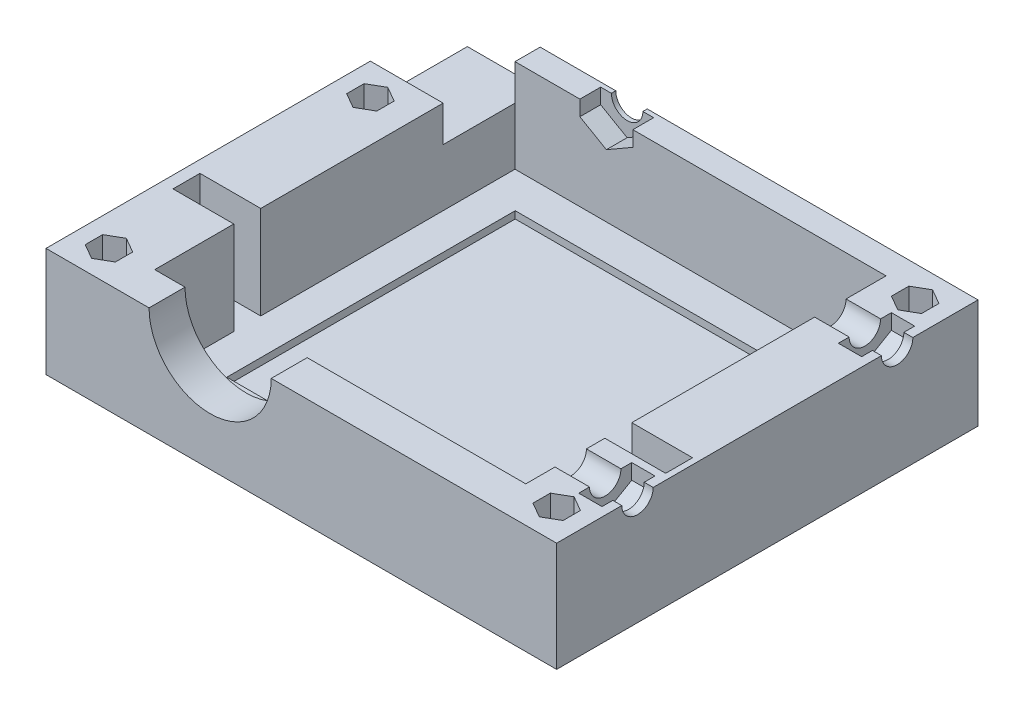
SolidWorks part; units mm, degrees
material "PLA"
ref_plane "Front Plane" through (0, 0, 0) normal (0, 0, 1) x (1, 0, 0)
ref_plane "Top Plane" through (0, 0, 0) normal (0, 1, 0) x (1, 0, 0)
ref_plane "Right Plane" through (0, 0, 0) normal (1, 0, 0) x (0, 0, -1)
sketch "Sketch1" plane through (0, 0, 0) normal (0, 1, 0) x (1, 0, 0)
  line L1 (28.4162, -23.45) -> (-28.4163, -23.45)
  line L2 (28.4162, -23.45) -> (28.4162, 23.45)
  line L3 (28.4162, 23.45) -> (-28.4163, 23.45)
  line L4 (-28.4163, -23.45) -> (-28.4163, 23.45)
  line L5 (28.4162, -23.45) -> (-28.4163, 23.45) construction
  line L6 (28.4162, 23.45) -> (-28.4163, -23.45) construction
  point P0 (0, 0)
  dimension "D1" = 56.8325
  dimension "D2" = 46.9
extrude "Boss-Extrude1" add sketch "Sketch1" along normal blind 12.17
sketch "Sketch2" plane through (0, 12.17, 0) normal (0, 1, 0) x (1, 0, 0)
  line L0 (-28.4163, -23.45) -> (-20.3162, -23.45) construction
  line L1 (-28.4163, -23.45) -> (28.4162, -23.45) construction
  line L2 (-20.3162, -23.45) -> (-20.3162, -19.45) construction
  line L4 (-20.3162, -19.45) -> (20.9838, -19.45)
  line L5 (-20.3162, -19.45) -> (-20.3162, 20.65)
  line L6 (-20.3162, 20.65) -> (20.9838, 20.65)
  line L7 (20.9838, -19.45) -> (20.9838, 20.65)
  dimension "D1" = 8.1
  dimension "D2" = 4
  dimension "D3" = 41.3
  dimension "D4" = 40.1
extrude "Cut-Extrude1" cut sketch "Sketch2" against normal blind 10.37
sketch "Sketch3" plane through (0, 1.8, 0) normal (0, 1, 0) x (1, 0, 0)
  line L0 (20.9838, 20.65) -> (20.9838, 16.6622) construction
  line L1 (20.9838, -19.45) -> (20.9838, 20.65) construction
  line L2 (20.9838, 16.6622) -> (16.996, 16.6622) construction
  line L4 (16.996, 16.6622) -> (-16.3041, 16.6622)
  line L5 (16.996, 16.6622) -> (16.996, -15.4378)
  line L6 (16.996, -15.4378) -> (-16.3041, -15.4378)
  line L7 (-16.3041, 16.6622) -> (-16.3041, -15.4378)
  dimension "D1" = 3.9878
  dimension "D2" = 3.9878
  dimension "D3" = 32.1
  dimension "D4" = 33.3
extrude "Cut-Extrude2" cut sketch "Sketch3" against normal blind 0.8
sketch "Sketch4" plane through (0, 12.17, 0) normal (0, 1, 0) x (1, 0, 0)
  line L0 (-20.3162, 20.65) -> (-20.3162, -19.45) construction
  line L1 (-28.4163, 23.45) -> (-20.3162, 23.45)
  line L2 (-28.4163, 23.45) -> (-28.4163, 12.65)
  line L3 (-28.4163, 12.65) -> (-20.3162, 12.65)
  line L4 (-20.3162, 23.45) -> (-20.3162, 12.65)
  dimension "D1" = 10.8
extrude "Cut-Extrude3" cut sketch "Sketch4" against normal blind 4
sketch "Sketch5" plane through (0, 12.17, 0) normal (0, 1, 0) x (1, 0, 0)
  line L0 (-28.4163, 12.65) -> (-28.4163, -7.65)
  line L1 (-28.4163, 12.65) -> (-28.4163, -23.45) construction
  line L2 (-28.4163, -7.65) -> (-27.0813, -7.65)
  line L3 (-20.3162, 20.65) -> (-20.3162, -19.45) construction
  line L4 (-27.0813, -7.65) -> (-20.3162, -7.65)
  line L5 (-27.0813, -7.65) -> (-27.0813, -10.65)
  line L6 (-27.0813, -10.65) -> (-20.3162, -10.65)
  line L7 (-20.3162, -7.65) -> (-20.3162, -10.65)
  line M11 (-20.3162, -19.45) -> (-20.3162, 12.65)
  dimension "D1" = 20.3
  dimension "D2" = 1.335
  dimension "D3" = 3
extrude "Cut-Extrude4" cut sketch "Sketch5" against normal up to surface (10.37 mm away) contours L5 L6 L4 M11 | L5 L4 L7 L6 region at (-23.6987, 12.17, 9.15) up to face at (0.3338, 1.8, -0.6)
sketch "Sketch6" plane through (0, 12.17, 0) normal (0, 1, 0) x (1, 0, 0)
  line L0 (-20.3162, -10.65) -> (20.9838, -10.65) construction
  line L2 (20.9838, -19.45) -> (20.9838, 20.65) construction
  line L3 (20.9838, -10.65) -> (27.7488, -10.65)
  line L4 (20.9838, -10.65) -> (20.9838, -7.65)
  line L5 (20.9838, -7.65) -> (27.7488, -7.65)
  line L6 (27.7488, -10.65) -> (27.7488, -7.65)
  line M15 (20.9838, 20.65) -> (20.9838, -19.45)
  dimension "D1" = 6.765
extrude "Cut-Extrude5" cut sketch "Sketch6" against normal up to surface (10.37 mm away) contours L3 L6 L5 M15 region at (24.3663, 12.17, 9.15) up to face at (-11.6825, 1.8, 4.275)
sketch "Sketch7" plane through (0, 0, 23.45) normal (0, 0, 1) x (1, 0, 0)
  line L0 (-28.4163, 12.17) -> (-16.9462, 12.17) construction
  line L1 (-28.4163, 12.17) -> (28.4162, 12.17) construction
  line L2 (-16.9462, 12.17) -> (-3.3462, 12.17)
  line L3 (-16.9462, 12.17) -> (-16.9462, 5.37) construction
  line L4 (-16.9462, 5.37) -> (-10.1462, 5.37) construction
  arc A0 (-16.9462, 12.17) -> (-3.3462, 12.17) centre (-10.1462, 12.17) ccw
  line M8 (28.4162, 12.17) -> (-28.4163, 12.17)
  dimension "D1" = 13.6
  dimension "D2" = 6.8
  dimension "D3" = 6.8
  dimension "D4" = 11.47
extrude "Cut-Extrude6" cut sketch "Sketch7" against normal up to surface (4 mm away) contours A0 M8 region at (-10.1462, 9.284, 23.45) up to face at (0.3338, 6.985, 19.45)
sketch "Sketch8" plane through (0, 12.17, 0) normal (0, 1, 0) x (1, 0, 0)
  line L0 (-28.4163, -23.45) -> (-24.9163, -23.45) construction
  line L1 (-28.4163, -23.45) -> (-16.9462, -23.45) construction
  line L2 (-24.9163, -23.45) -> (-24.9163, -21.8752) construction
  line L3 (-24.9163, -21.8752) -> (-24.9163, -18.007) construction
  line L4 (-24.9163, -18.007) -> (-24.9163, 7.2248) construction
  line L5 (-24.9163, -18.007) -> (-26.5913, -18.974)
  line L6 (-26.5913, -18.974) -> (-26.5913, -20.9081)
  line L7 (-26.5913, -20.9081) -> (-24.9163, -21.8752)
  line L8 (-24.9163, -21.8752) -> (-23.2413, -20.9081)
  line L9 (-23.2413, -20.9081) -> (-23.2413, -18.974)
  line L10 (-23.2413, -18.974) -> (-24.9163, -18.007)
  line L11 (-24.9163, 7.2248) -> (-24.9163, 11.093) construction
  line L12 (-24.9163, -21.8752) -> (24.9162, -21.8752) construction
  line L13 (-24.9163, 11.093) -> (-26.5913, 10.126)
  line L14 (-26.5913, 10.126) -> (-26.5913, 8.1918)
  line L15 (-26.5913, 8.1918) -> (-24.9163, 7.2248)
  line L16 (-24.9163, 7.2248) -> (-23.2413, 8.1918)
  line L17 (-23.2413, 8.1918) -> (-23.2413, 10.126)
  line L18 (-23.2413, 10.126) -> (-24.9163, 11.093)
  line L19 (24.9162, -21.8752) -> (24.9162, -18.007) construction
  line L20 (24.9162, -18.007) -> (24.9162, 18.0248) construction
  line L21 (24.9162, 18.0248) -> (24.9162, 21.893) construction
  line L23 (24.9162, 21.893) -> (23.2412, 20.926)
  line L24 (23.2412, 20.926) -> (23.2412, 18.9919)
  line L25 (23.2412, 18.9919) -> (24.9162, 18.0248)
  line L26 (24.9162, 18.0248) -> (26.5912, 18.9919)
  line L27 (26.5912, 18.9919) -> (26.5912, 20.926)
  line L28 (26.5912, 20.926) -> (24.9162, 21.893)
  line L29 (24.9162, -18.007) -> (23.2412, -18.974)
  line L30 (23.2412, -18.974) -> (23.2412, -20.9081)
  line L31 (23.2412, -20.9081) -> (24.9162, -21.8752)
  line L32 (24.9162, -21.8752) -> (26.5912, -20.9081)
  line L33 (26.5912, -20.9081) -> (26.5912, -18.974)
  line L34 (26.5912, -18.974) -> (24.9162, -18.007)
  circle A0 centre (-24.9163, -19.9411) radius 1.675 construction
  circle A1 centre (-24.9163, 9.1589) radius 1.675 construction
  circle A2 centre (24.9162, 19.9589) radius 1.675 construction
  circle A3 centre (24.9162, -19.9411) radius 1.675 construction
  dimension "D1" = 3.5
  dimension "D2" = 1.5748
  dimension "D3" = 3.8682
  dimension "D4" = 25.2318
  dimension "D5" = 3.8682
  dimension "D6" = 49.8325
  dimension "D7" = 3.8682
  dimension "D8" = 36.0318
  dimension "D9" = 3.8682
extrude "Cut-Extrude7" cut sketch "Sketch8" against normal blind 5.25
sketch "Sketch9" plane through (0, 6.92, 0) normal (0, 1, 0) x (1, 0, 0)
  line L0 (-24.9163, 11.093) -> (-24.9163, 7.2248) construction
  line L1 (-24.9163, 7.2248) -> (-24.2368, 7.2248) construction
  line L2 (-26.5913, 10.126) -> (-26.5913, 8.1918) construction
  line L3 (-26.5913, 9.1589) -> (-23.2413, 9.1589) construction
  line L4 (-23.2413, 8.1918) -> (-23.2413, 10.126) construction
  line L5 (-24.2368, 7.2248) -> (-24.2368, 8.0608) construction
  line L6 (-24.2368, 8.0608) -> (-25.5134, 8.0608) construction
  line L7 (-25.5134, 8.0608) -> (-25.5134, 10.257) construction
  line L8 (-24.9163, 9.1589) -> (-24.9163, -18.007) construction
  line L9 (-24.9163, -18.007) -> (-24.9163, -21.8752) construction
  line L10 (-24.9163, -21.8752) -> (24.9162, -21.8752) construction
  line L11 (24.9162, -21.8752) -> (24.9162, -18.007) construction
  line L12 (24.9162, -18.007) -> (24.9162, 18.0248) construction
  line L13 (24.9162, 18.0248) -> (24.9162, 21.893) construction
  circle A1 centre (-24.8751, 9.1589) radius 1.2702
  circle A2 centre (-24.9163, -19.9411) radius 1.2702
  circle A3 centre (24.9162, -19.9411) radius 1.2702
  circle A4 centre (24.9162, 19.9589) radius 1.2702
  dimension "D5" = 2.5404
  dimension "D6" = 2.5404
  dimension "D7" = 2.5404
  dimension "D8" = 2.5404
  dimension "D1" = 0.6794
  dimension "D2" = 0.836
  dimension "D3" = 1.2766
  dimension "D4" = 2.1963
extrude "Cut-Extrude8" cut sketch "Sketch9" against normal through all
sketch "Sketch10" plane through (0, 0, 23.45) normal (0, 0, 1) x (1, 0, 0)
  line L0 (-16.9462, 12.17) -> (-13.0962, 12.17) construction
  line L1 (-13.0962, 12.17) -> (-10.1462, 12.17) construction
  line L2 (-10.1462, 12.17) -> (-10.1462, 8.7636) construction
  line L4 (-10.1462, 8.7664) -> (-7.1986, 10.4682)
  line L5 (-7.1986, 10.4682) -> (-7.1986, 13.8718)
  line L6 (-7.1986, 13.8718) -> (-10.1462, 15.5736)
  line L7 (-10.1462, 15.5736) -> (-13.0938, 13.8718)
  line L8 (-13.0938, 13.8718) -> (-13.0938, 10.4682)
  line L9 (-13.0938, 10.4682) -> (-10.1462, 8.7664)
  arc A0 (-16.9462, 12.17) -> (-3.3462, 12.17) centre (-10.1462, 12.17) ccw construction
  circle A1 centre (-10.1462, 12.17) radius 2.9476 construction
  point P7 (-10.1462, 10.4668)
  dimension "D1" = 3.85
  dimension "D2" = 3.4064
  dimension "D3" = 2.95
  dimension "D4" = 3.4036
sketch "Sketch11" plane through (0, 0, -20.65) normal (0, 0, 1) x (1, 0, 0)
  line L0 (-13.0938, 10.4682) -> (-10.1462, 8.7664) construction
  line L1 (-10.1462, 8.7664) -> (-7.1986, 10.4682) construction
  line L2 (-7.1986, 10.4682) -> (-7.1986, 13.8718) construction
  line L3 (-13.0938, 13.8718) -> (-13.0938, 10.4682) construction
  line L4 (-10.1462, 15.5736) -> (-13.0938, 13.8718) construction
  line L5 (-7.1986, 13.8718) -> (-10.1462, 15.5736) construction
  line L6 (-13.0938, 10.4682) -> (-10.1462, 8.7664)
  line L7 (-10.1462, 8.7664) -> (-7.1986, 10.4682)
  line L8 (-7.1986, 10.4682) -> (-7.1986, 13.8718)
  line L9 (-13.0938, 13.8718) -> (-13.0938, 10.4682)
  line L10 (-10.1462, 15.5736) -> (-13.0938, 13.8718)
  line L11 (-7.1986, 13.8718) -> (-10.1462, 15.5736)
extrude "Cut-Extrude10" cut sketch "Sketch11" against normal blind 2.3114
sketch "Sketch12" plane through (0, 0, -22.9614) normal (0, 0, 1) x (1, 0, 0)
  line L5 (-13.0938, 12.17) -> (-13.0938, 10.4682)
  line L6 (-13.0938, 10.4682) -> (-10.1462, 8.7664)
  line L7 (-10.1462, 8.7664) -> (-7.1986, 10.4682)
  line L8 (-7.1986, 10.4682) -> (-7.1986, 12.17)
  line L9 (-7.1986, 12.17) -> (-13.0938, 12.17)
  line L10 (-13.0938, 12.17) -> (-13.0938, 10.4682)
  line L11 (-13.0938, 10.4682) -> (-10.1462, 8.7664) construction
  line L12 (-10.1462, 8.7664) -> (-7.1986, 10.4682) construction
  line L13 (-7.1986, 10.4682) -> (-7.1986, 12.17) construction
  line L14 (-7.1986, 12.17) -> (-13.0938, 12.17) construction
  circle A0 centre (-10.1462, 12.17) radius 1.75
  line M11 (-7.1986, 12.17) -> (-13.0938, 12.17)
  dimension "D2" = 3.5
  dimension "D1" = 0
extrude "Cut-Extrude11" cut sketch "Sketch12" against normal up to surface (0.4886 mm away) contours A0 M11 | A0 M11 region at (-10.1462, 12.9127, -22.9614) region at (-10.1462, 11.4273, -22.9614) up to face at (-6.7721, 6.78, -23.45)
sketch "Sketch13" plane through (28.4162, 0, 0) normal (1, 0, 0) x (0, 0, -1)
  line L0 (-23.45, 12.17) -> (-16.2, 12.17) construction
  line L1 (-23.45, 12.17) -> (23.45, 12.17) construction
  line L2 (-16.2, 12.17) -> (-12.7, 12.17) construction
  line L3 (-12.7, 12.17) -> (12.7, 12.17) construction
  line L4 (12.7, 12.17) -> (16.2, 12.17) construction
  circle A0 centre (-14.45, 12.17) radius 1.75
  circle A1 centre (14.45, 12.17) radius 1.75
  line M7 (23.45, 12.17) -> (-23.45, 12.17)
  dimension "D1" = 3.5
  dimension "D2" = 7.25
  dimension "D3" = 25.4
  dimension "D4" = 3.5
extrude "Cut-Extrude12" cut sketch "Sketch13" against normal up to surface (7.4325 mm away) contours A1 M7 | A0 M7 | A0 M7 | A1 M7 region at (28.4162, 12.9127, 14.45) region at (28.4162, 12.9127, -14.45) region at (28.4162, 11.4273, -14.45) region at (28.4162, 11.4273, 14.45) up to face at (20.9838, 6.985, -6.5)
sketch "Sketch14" plane through (0, 12.17, 0) normal (0, 1, 0) x (1, 0, 0)
  line L0 (28.4162, -23.45) -> (28.4162, -17.4) construction
  line L1 (28.4162, -23.45) -> (28.4162, -16.2) construction
  line L2 (28.4162, -17.4) -> (27.4163, -17.4) construction
  line L3 (27.4163, -17.4) -> (27.4163, -11.5)
  line L4 (27.4163, -17.4) -> (24.8255, -17.4)
  line L5 (27.4163, -11.5) -> (24.8255, -11.5)
  line L6 (24.8255, -11.5) -> (24.8255, -17.4)
  dimension "D1" = 1
  dimension "D2" = 6.05
  dimension "D3" = 5.9
  dimension "D4" = 2.5908
extrude "Cut-Extrude13" cut sketch "Sketch14" against normal blind 1.7032
sketch "Sketch16" plane through (27.4163, 0, 0) normal (-1, 0, 0) x (0, 0, 1)
  line L1 (17.4, 12.17) -> (17.4, 10.4668) construction
  line L4 (11.5, 10.4668) -> (11.5, 12.17) construction
  line L7 (17.4, 12.17) -> (17.4, 10.4668)
  line L10 (11.5, 10.4668) -> (11.5, 12.17)
  line L12 (17.4, 12.17) -> (11.5, 12.17)
  line L13 (17.4, 10.4668) -> (14.45, 8.7636)
  line L14 (14.45, 8.7636) -> (11.5, 10.4668)
  line L15 (14.45, 8.7636) -> (14.45, 12.17) construction
  line L16 (11.5, 12.17) -> (-11.5, 12.17) construction
  line L17 (0, 12.17) -> (0, 18.4152) construction
  line L18 (-17.4, 12.17) -> (-17.4, 10.4668)
  line L19 (-17.4, 12.17) -> (-11.5, 12.17)
  line L20 (-11.5, 10.4668) -> (-11.5, 12.17)
  line L21 (-14.45, 8.7636) -> (-11.5, 10.4668)
  line L22 (-17.4, 10.4668) -> (-14.45, 8.7636)
  line M9 (14.8521, 10.4668) -> (17.4, 10.4668)
  arc M12 (16.2, 12.17) -> (14.8521, 10.4668) centre (14.45, 12.17) cw
  dimension "D1" = 3.4064
  dimension "D2" = 23
extrude "Cut-Extrude15" cut sketch "Sketch16" along normal up to surface (2.5908 mm away) contours L14 L13 L12 L10 M9 M12 | L18 L22 L21 L20 L19 region at (27.4163, 10.7672, 13.9978) region at (27.4163, 10.8453, -14.45) up to face at (24.8255, 11.2598, 12.3629)
